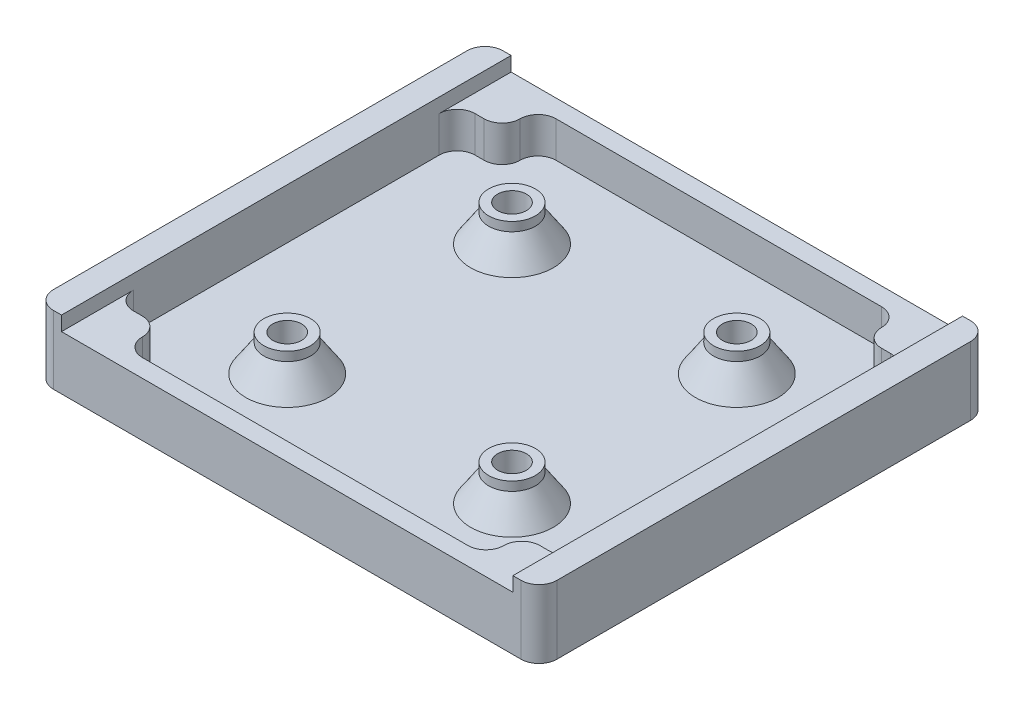
SolidWorks part; units mm, degrees
ref_plane "前视基准面" through (0, 0, 0) normal (0, 0, 1) x (1, 0, 0)
ref_plane "上视基准面" through (0, 0, 0) normal (0, 1, 0) x (1, 0, 0)
ref_plane "右视基准面" through (0, 0, 0) normal (1, 0, 0) x (0, 0, -1)
sketch "草图1" plane through (0, 0, 0) normal (0, 1, 0) x (1, 0, 0)
  line L1 (-28, 25) -> (28, 25)
  line L2 (-28, 25) -> (-28, -25)
  line L3 (-28, -25) -> (28, -25)
  line L4 (28, 25) -> (28, -25)
  line L5 (-28, 25) -> (28, -25) construction
  line L6 (-28, -25) -> (28, 25) construction
  line L7 (-12.5, 12.5) -> (12.5, 12.5) construction
  line L8 (-12.5, 12.5) -> (-12.5, -12.5) construction
  line L9 (-12.5, -12.5) -> (12.5, -12.5) construction
  line L10 (12.5, 12.5) -> (12.5, -12.5) construction
  line L11 (-12.5, 12.5) -> (12.5, -12.5) construction
  line L12 (-12.5, -12.5) -> (12.5, 12.5) construction
  circle A0 centre (-12.5, 12.5) radius 1.6
  circle A1 centre (12.5, 12.5) radius 1.6
  circle A2 centre (12.5, -12.5) radius 1.6
  circle A5 centre (-12.5, -12.5) radius 1.6
  point P0 (0, 0)
  point P6 (0, 0)
  dimension "D2" = 25
  dimension "D6" = 3.2
  dimension "D4" = 3.2
  dimension "D5" = 3.2
  dimension "D8" = 3.2
  dimension "D1" = 50
  dimension "D3" = 25
  dimension "D7" = 56
extrude "凸台-拉伸1" add sketch "草图1" along normal blind 7.6
sketch "草图2" plane through (0, 7.6, 0) normal (0, 1, 0) x (1, 0, 0)
  line L0 (-28, 25) -> (-28, -25) construction
  line L1 (28, -25) -> (28, 25) construction
  line L2 (28, -25) -> (28, 25)
  line L3 (-28, 25) -> (-28, -25)
  line L4 (-25.1, 25) -> (-25.1, -25)
  line L5 (25.1, -25) -> (25.1, 25)
  line L6 (-25.1, 25) -> (25.1, 25)
  line L7 (25.1, -25) -> (-25.1, -25)
  circle M5 centre (12.5, -12.5) radius 1.6
  circle M6 centre (-12.5, 12.5) radius 1.6
  line M8 (28, 25) -> (-28, 25)
  line M10 (-28, -25) -> (28, -25)
  circle M11 centre (12.5, 12.5) radius 1.6
  circle M12 centre (-12.5, -12.5) radius 1.6
  dimension "D1" = 2.9
extrude "切除-拉伸1" cut sketch "草图2" against normal blind 1.6 contours L5 L4 M10 M8 M6 M11 M12 M5 region at (0, 7.6, 0)
sketch "草图3" plane through (0, 6, 0) normal (0, 1, 0) x (1, 0, 0)
  line L4 (-25.1, -25) -> (25.1, -25)
  line L5 (25.1, -25) -> (25.1, 25)
  line L7 (-25.1, 25) -> (-25.1, -25)
  line L9 (25.1, -25) -> (25.1, 25)
  line L11 (-25.1, 25) -> (-25.1, -25)
  line L12 (-20.1, 25) -> (-20.1, -25)
  line L13 (20.1, -25) -> (20.1, 25)
  line L14 (-25.1, 19) -> (25.1, 19)
  line L15 (-25.1, -19) -> (25.1, -19)
  line L20 (-25.1, -25) -> (25.1, -25)
  line L22 (25.1, 25) -> (-25.1, 25)
  line L23 (25.1, 25) -> (-25.1, 25)
  circle M11 centre (-12.5, 12.5) radius 1.6
  circle M12 centre (12.5, 12.5) radius 1.6
  circle M13 centre (-12.5, -12.5) radius 1.6
  circle M14 centre (12.5, -12.5) radius 1.6
  dimension "D3" = 6
  dimension "D4" = 6
  dimension "D1" = 0
  dimension "D2" = 5
extrude "切除-拉伸2" cut sketch "草图3" against normal blind 4 contours L12 L15 L13 L14 M12 M14 M13 M11 | L12 L14 L13 L23 | L13 L15 L9 L14 | L11 L15 L12 L14 | L15 L12 L20 L13 region at (0, 6, 22) region at (-22.6, 6, 0) region at (0, 6, 0) region at (22.6, 6, 0) region at (0, 6, -22)
sketch "草图4" plane through (0, 2, 0) normal (0, 1, 0) x (1, 0, 0)
  circle A0 centre (-12.5, -12.5) radius 1.6 construction
  circle A1 centre (12.5, -12.5) radius 1.6 construction
  circle A2 centre (12.5, 12.5) radius 1.6 construction
  circle A3 centre (-12.5, 12.5) radius 1.6 construction
  circle A4 centre (-12.5, -12.5) radius 1.6
  circle A5 centre (12.5, -12.5) radius 1.6
  circle A6 centre (12.5, 12.5) radius 1.6
  circle A7 centre (-12.5, 12.5) radius 1.6
  circle A9 centre (-12.5, 12.5) radius 2.6
  circle A10 centre (12.5, 12.5) radius 2.6
  circle A11 centre (12.5, -12.5) radius 2.6
  circle A12 centre (-12.5, -12.5) radius 2.6
  dimension "D1" = 1
extrude "凸台-拉伸2" add sketch "草图4" along normal blind 4
ref_axis "基准轴1" through (-12.5, 6, 12.5) along (0, -1, 0)
ref_plane "基准面1" through (0, 0, 12.5) normal (0, 0, 1) x (1, 0, 0)
sketch "草图5" plane through (0, 0, 12.5) normal (0, 0, 1) x (1, 0, 0)
  line L0 (-9.9, 5) -> (-7.9, 2)
  line L1 (-9.9, 2) -> (-9.9, 6) construction
  line L2 (-20.1, 2) -> (20.1, 2) construction
  line L3 (-9.9, 6) -> (-15.1, 6) construction
  line L4 (-9.9, 5) -> (-9.9, 2)
  line L5 (-9.9, 2) -> (-7.9, 2)
  dimension "D1" = 1
  dimension "D2" = 2
sketch "草图6" plane through (0, 2, 0) normal (0, 1, 0) x (1, 0, 0)
  line L0 (-20.1, -25) -> (20.1, -25) construction
  line L1 (20.1, 25) -> (-20.1, 25) construction
  line L2 (-20.1, -25) -> (20.1, -25)
  line L3 (20.1, 25) -> (-20.1, 25)
  line L4 (20.1, 23) -> (-20.1, 23)
  line L5 (-20.1, -23) -> (20.1, -23)
  line L6 (-20.1, 23) -> (-20.1, 25)
  line L7 (20.1, 25) -> (20.1, 23)
  line L8 (20.1, -25) -> (20.1, -23)
  line L9 (-20.1, -25) -> (-20.1, -23)
  dimension "D1" = 2
extrude "凸台-拉伸3" add sketch "草图6" along normal up to surface (4 mm away) up to face at (-22.6, 6, 22)
fillet "圆角2" radius 2 16 edges at (25.1, 4, 19) (20.1, 4, 19) (20.1, 4, 23) (-28, 3.8, -25) (-28, 3.8, 25) (28, 3.8, 25) (28, 3.8, -25) (-20.1, 4, 23) (-25.1, 4, 19) (-20.1, 4, 19) (25.1, 4, -19) (20.1, 4, -19) (20.1, 4, -23) (-20.1, 4, -23) (-20.1, 4, -19) (-25.1, 4, -19)
revolve "旋转1" add sketch "草图5" angle 360 about axis through (-12.5, 6, 12.5) along (0, -1, 0)
sketch "草图7" plane through (0, 0, 0) normal (0, -1, 0) x (1, 0, 0)
  circle A0 centre (-12.5, 12.5) radius 2.8
  dimension "D1" = 5.6
extrude "切除-拉伸3" cut sketch "草图7" against normal blind 3.2
ref_axis "基准轴2" through (0, 0, 0) along (0, 1, 0)
pattern_circular "阵列(圆周)2" count 4 over 360 about axis through (0, 0, 0) along (0, 1, 0) of "旋转1", "切除-拉伸3"
